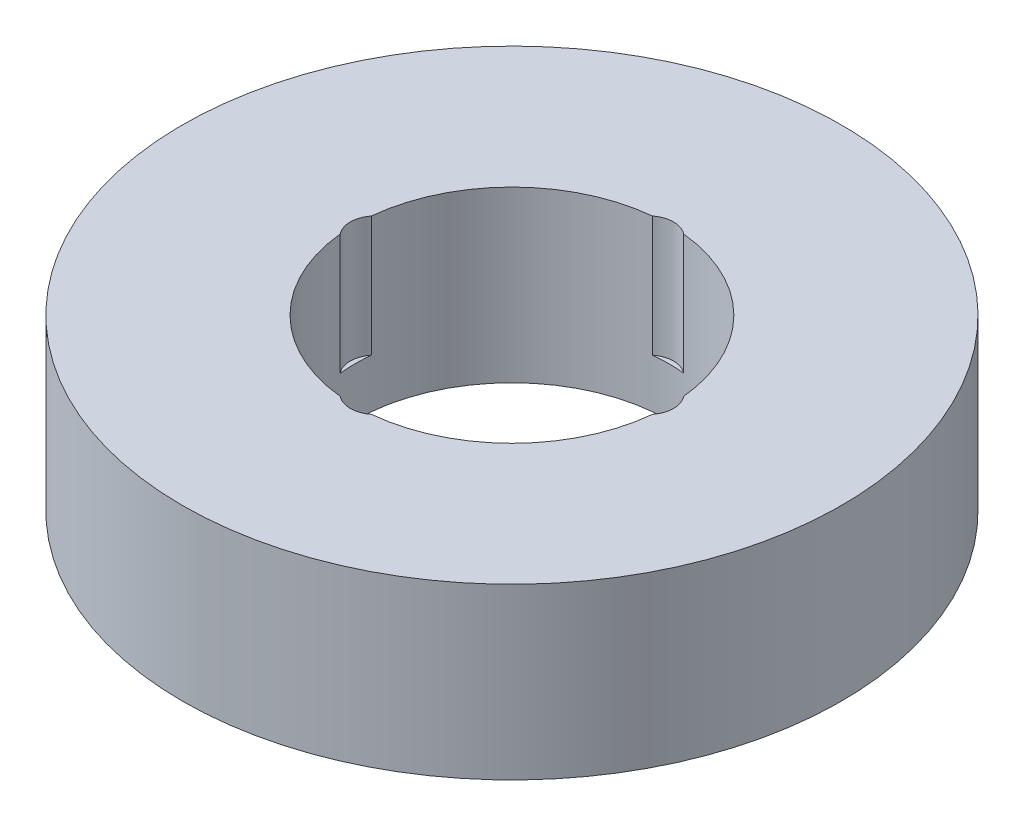
SolidWorks part; units mm, degrees
ref_plane "Front Plane" through (0, 0, 0) normal (0, 0, 1) x (1, 0, 0)
ref_plane "Top Plane" through (0, 0, 0) normal (0, 1, 0) x (1, 0, 0)
ref_plane "Right Plane" through (0, 0, 0) normal (1, 0, 0) x (0, 0, -1)
sketch "Sketch1" plane through (0, 0, 0) normal (0, 1, 0) x (1, 0, 0)
  circle A0 centre (0, 0) radius 52.5
  dimension "FLANGE_OD" = 105
extrude "Boss-Extrude1" add sketch "Sketch1" along normal blind 27
sketch "Sketch2" plane through (0, 0, 0) normal (0, 1, 0) x (1, 0, 0)
  circle A0 centre (0, 0) radius 25
  dimension "BORE_D" = 50
extrude "Cut-Extrude1" cut sketch "Sketch2" along normal through all
sketch "Sketch3" plane through (0, 27, 0) normal (0, 1, 0) x (1, 0, 0)
  circle A0 centre (0, 0) radius 21.7381 construction
  circle A1 centre (-21.7381, 0) radius 4.0031
  dimension "BOLT_D" = 8.0062
  dimension "BOLT_PCD" = 43.4763
extrude "Cut-Extrude2" cut sketch "Sketch3" against normal blind 19.1934
pattern_circular "CirPattern1" count 4 over 360 about axis through (0, 0, 0) along (0, 1, 0) of "Cut-Extrude2"
